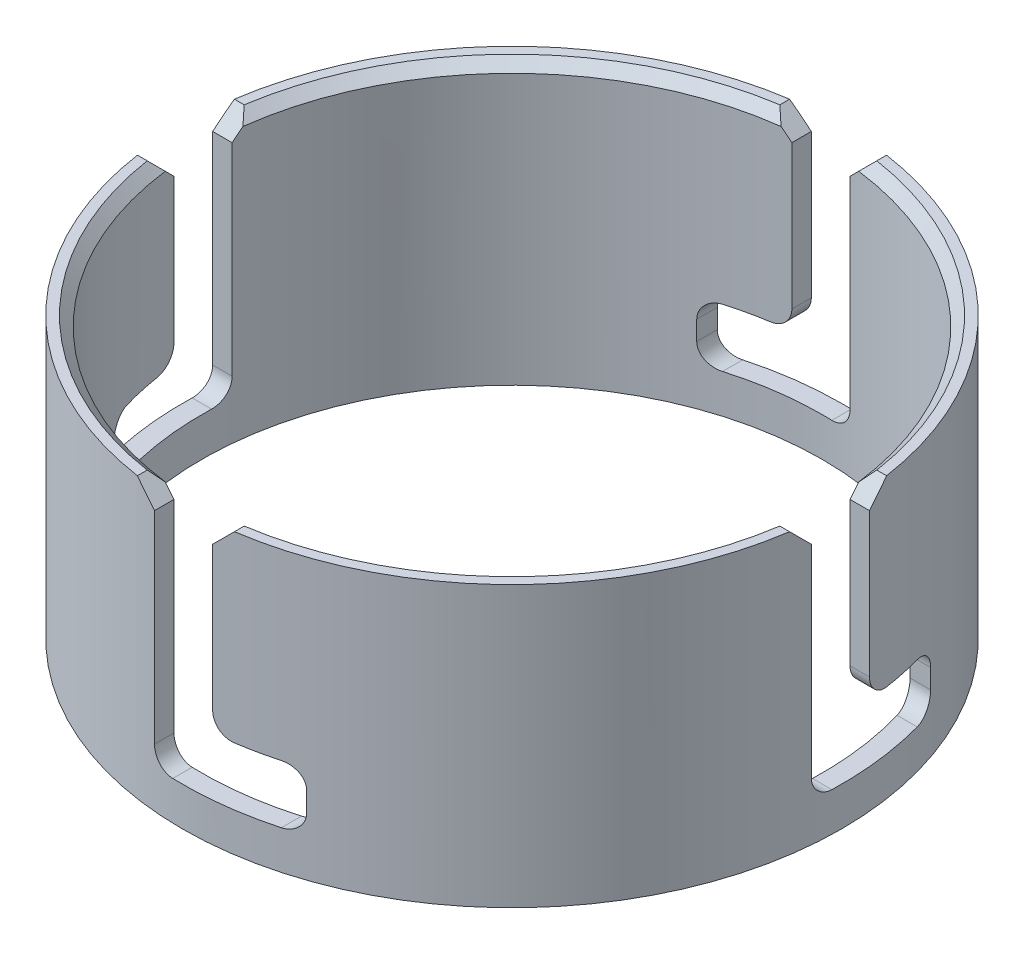
SolidWorks part; units mm, degrees
ref_plane "Front Plane" through (0, 0, 0) normal (0, 0, 1) x (1, 0, 0)
ref_plane "Top Plane" through (0, 0, 0) normal (0, 1, 0) x (1, 0, 0)
ref_plane "Right Plane" through (0, 0, 0) normal (1, 0, 0) x (0, 0, -1)
sketch "Sketch2" plane through (0, 0, 0) normal (1, 0, 0) x (0, 0, -1)
  line L0 (-79.9998, 0) -> (-84.9998, 0)
  line L1 (-84.9998, 0) -> (-84.9998, 72.15)
  line L2 (-84.9998, 72.15) -> (-79.9998, 72.15)
  line L5 (-79.9998, 72.15) -> (-79.9998, 0)
  dimension "D1" = 84.9998
  dimension "D2" = 72.15
  dimension "D3" = 5
ref_axis "Axis1" through (0, -0.75, 0) along (0, 1, 0)
revolve "Revolve1" add sketch "Sketch2" angle 360 about axis through (0, -0.75, 0) along (0, 1, 0)
sketch "Sketch3" plane through (0, 0, 0) normal (1, 0, 0) x (0, 0, -1)
  line L0 (-7.5, 72.15) -> (7.5, 72.15)
  line L1 (84.9998, 72.15) -> (-84.9998, 72.15) construction
  line L2 (7.5, 72.15) -> (7.5, 10)
  line L3 (7.5, 10) -> (-27.5, 10)
  line L4 (-27.5, 10) -> (-27.5, 25)
  line L5 (-27.5, 25) -> (-7.5, 25)
  line L6 (-7.5, 25) -> (-7.5, 72.15)
  line L7 (0, -0.75) -> (0, 15.75) construction
  line L8 (0, 0) -> (0, 47.5309) construction
  line L9 (-84.9998, 0) -> (84.9998, 0) construction
  point P6 (0, 0)
  dimension "D1" = 10
  dimension "D2" = 15
  dimension "D3" = 15
  dimension "D4" = 20
extrude "Cut-Extrude1" cut sketch "Sketch3" against normal through all
fillet "Fillet1" radius 5 2 edges at (-82.1579, 25, 7.5) (-82.1579, 10, -7.5)
chamfer "Chamfer1" distance 5 angle 45 2 edges at (-82.1579, 72.15, 7.5) (-82.1579, 72.15, -7.5)
fillet "Fillet3" radius 5 2 edges at (-77.7765, 25, 27.5) (-77.7765, 10, 27.5)
pattern_circular "CirPattern1" count 4 over 360 about axis through (0, -0.75, 0) along (0, 1, 0) of "Fillet3", "Chamfer1", "Fillet1", "Cut-Extrude1"
chamfer "Chamfer2" distance 2.5 angle 45 4 edges at (-56.5684, 72.15, -56.5684) (56.5684, 72.15, -56.5684) (56.5684, 72.15, 56.5684) (-56.5684, 72.15, 56.5684)
